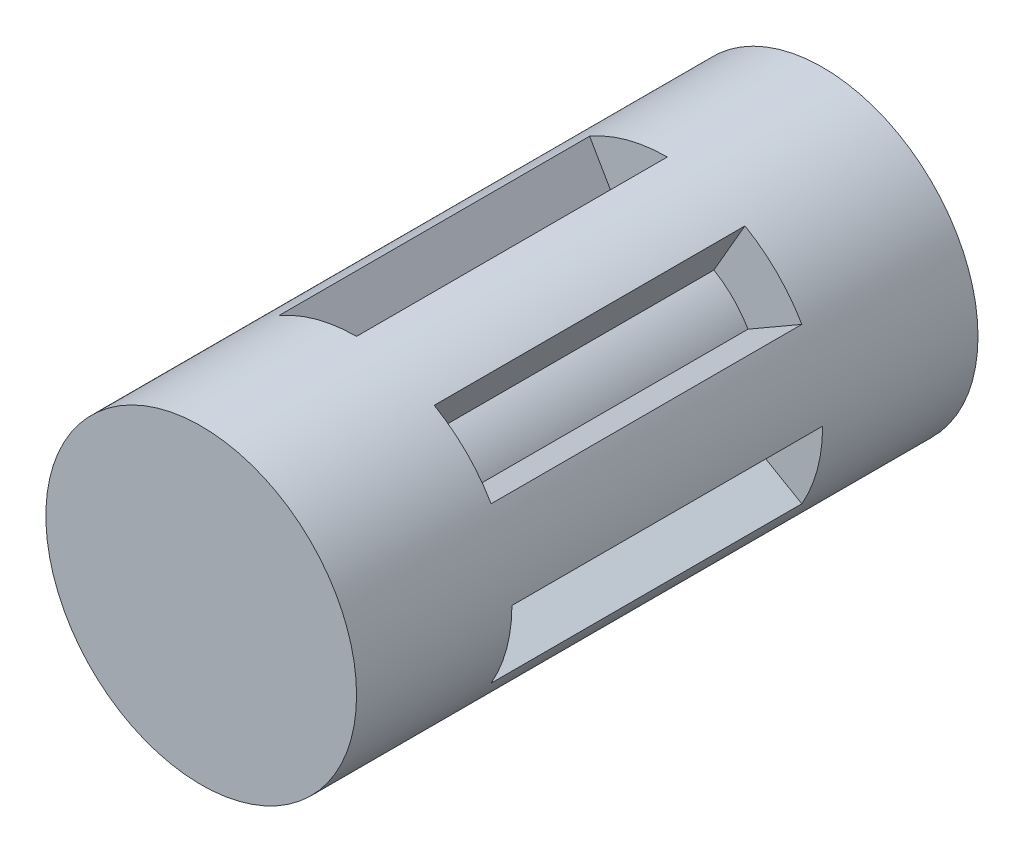
SolidWorks part; units mm, degrees
ref_plane "前视基准面" through (0, 0, 0) normal (0, 0, 1) x (1, 0, 0)
ref_plane "上视基准面" through (0, 0, 0) normal (0, 1, 0) x (1, 0, 0)
ref_plane "右视基准面" through (0, 0, 0) normal (1, 0, 0) x (0, 0, -1)
sketch "草图1" plane through (0, 0, 0) normal (0, 0, 1) x (1, 0, 0)
  circle A0 centre (0, 0) radius 2.5
  dimension "D1" = 5
extrude "凸台-拉伸1" add sketch "草图1" along normal blind 5
sketch "草图2" plane through (0, 0, 0) normal (0, 0, -1) x (-1, 0, 0)
  line L0 (0, 2.5) -> (0, 1.5)
  line L1 (0.75, 1.299) -> (1.25, 2.1651)
  arc A0 (0, 2.5) -> (1.25, 2.1651) centre (0, 0) cw
  circle A1 centre (0, 0) radius 2.5 construction
  arc A2 (0, 1.5) -> (0.75, 1.299) centre (0, 0) cw
  dimension "D1" = 30
  dimension "D2" = 1
extrude "切除-拉伸1" cut sketch "草图2" against normal blind 2.5
pattern_circular "阵列(圆周)1" count 6 over 360 about axis through (0, 0, 5) along (0, 0, 1) of "切除-拉伸1"
mirror "镜向1" about plane through (0, 0, 0) normal (0, 0, 1) of "凸台-拉伸1", "切除-拉伸1", "阵列(圆周)1"
